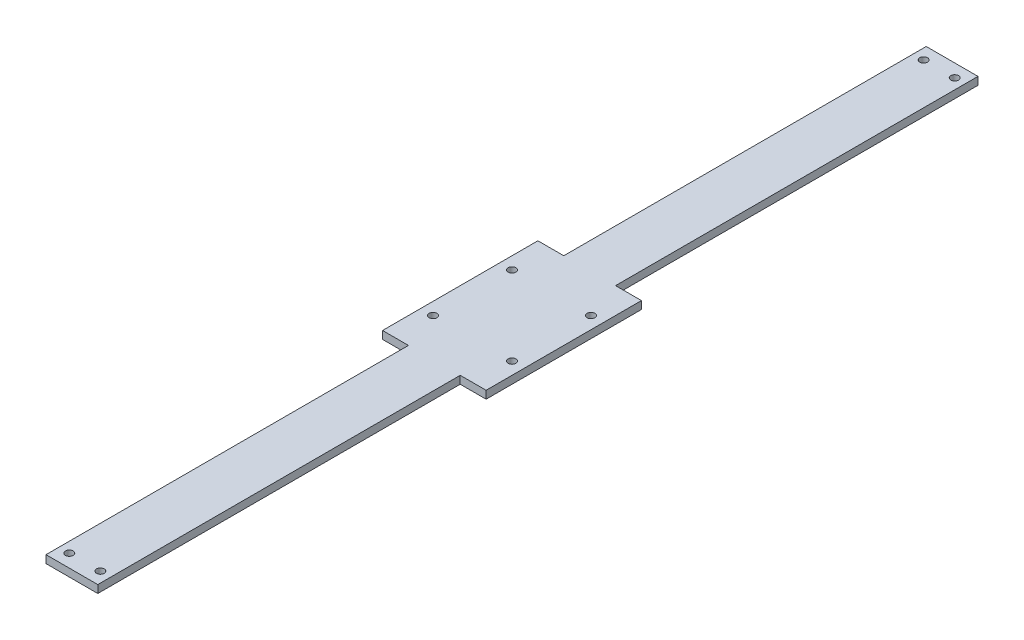
SolidWorks part; units mm, degrees
ref_plane "Front Plane" through (0, 0, 0) normal (0, 0, 1) x (1, 0, 0)
ref_plane "Top Plane" through (0, 0, 0) normal (0, 1, 0) x (1, 0, 0)
ref_plane "Right Plane" through (0, 0, 0) normal (1, 0, 0) x (0, 0, -1)
sketch "Sketch1" plane through (0, 0, 0) normal (0, 1, 0) x (1, 0, 0)
  line L5 (-10, 170) -> (-10, 30)
  line L6 (20, 170) -> (-20, 170) construction
  line L12 (20, 170) -> (20, -170) construction
  line L13 (20, -170) -> (-20, -170) construction
  line L24 (-20, 170) -> (-20, -170) construction
  line L25 (20, 170) -> (-20, -170) construction
  line L26 (20, -170) -> (-20, 170) construction
  line L27 (-10, 30) -> (-20, 30)
  line L28 (0, 170) -> (0, -170) construction
  line L29 (-20, 0) -> (20, 0) construction
  line L30 (10, 30) -> (20, 30)
  line L31 (10, 170) -> (10, 30)
  line L32 (-10, -30) -> (-20, -30)
  line L33 (-10, -170) -> (-10, -30)
  line L34 (10, -170) -> (10, -30)
  line L35 (10, -30) -> (20, -30)
  line L36 (-10, 170) -> (10, 170)
  line L37 (-10, -170) -> (10, -170)
  line L38 (-20, 30) -> (-20, -30)
  line L39 (20, 30) -> (20, -30)
  point P0 (0, 0)
  dimension "D2" = 40
  dimension "D1" = 340
  dimension "D3" = 10
  dimension "D4" = 30
ref_axis "yaw" through (0, 177.4955, 0) along (0, -1, 0)
extrude "Boss-Extrude1" add sketch "Sketch1" along normal mid plane 3
sketch "Sketch4" plane through (0, 1.5, 0) normal (0, 1, 0) x (1, 0, 0)
  line L1 (15.25, 15.25) -> (-15.25, 15.25)
  line L2 (15.25, 15.25) -> (15.25, -15.25)
  line L3 (15.25, -15.25) -> (-15.25, -15.25)
  line L4 (-15.25, 15.25) -> (-15.25, -15.25)
  line L5 (15.25, 15.25) -> (-15.25, -15.25) construction
  line L6 (15.25, -15.25) -> (-15.25, 15.25) construction
  point P0 (0, 0)
  dimension "D1" = 30.5
  dimension "D2" = 30.5
hole_wizard "fc mount hole" positions "Sketch5" profile "Sketch6" hole size "Ø3.0" standard "ISO" end condition through all
sketch "Sketch5" plane through (0, 1.5, 0) normal (0, 1, 0) x (1, 0, 0)
  point P0 (-15.25, 15.25)
  point P3 (15.25, 15.25)
  point P6 (15.25, -15.25)
  point P9 (-15.25, -15.25)
sketch "Sketch6" plane through (-15.25, 1.5, -15.25) normal (1, 0, 0) x (0, 0, 1)
  line L0 (0, 0) -> (0, 3)
  line L1 (0, 3) -> (1.5, 3)
  line L2 (1.5, 3) -> (1.5, 0)
  line L5 (1.5, 0) -> (0, 0)
  line L11 (0, -6.35) -> (0, 107.95) construction
  dimension "Thru Hole Dia." = 3
  dimension "Thru Hole Depth" = 3
sketch "Sketch7" plane through (0, 1.5, 0) normal (0, 1, 0) x (1, 0, 0)
  line L0 (0, -170) -> (0, 170) construction
  line L1 (-10, -170) -> (10, -170) construction
  line L2 (10, 170) -> (-10, 170) construction
  line L3 (-10, -165) -> (10, -165) construction
  line L4 (-10, -30) -> (-10, -170) construction
  line L5 (10, -170) -> (10, -30) construction
  line L6 (-20, 0) -> (20, 0) construction
  line L7 (-20, 30) -> (-20, -30) construction
  line L8 (20, -30) -> (20, 30) construction
  point P12 (-6, -165)
  point P13 (6, -165)
  dimension "D1" = 5
  dimension "D2" = 12
hole_wizard "Ø3.0 (3) Diameter Hole1" positions "Sketch8" profile "Sketch9" hole size "Ø3.0" standard "ISO" end condition through all
sketch "Sketch8" plane through (0, 1.5, 0) normal (0, 1, 0) x (1, 0, 0)
  point P0 (6, -165)
  point P3 (-6, -165)
sketch "Sketch9" plane through (6, 1.5, 165) normal (1, 0, 0) x (0, 0, 1)
  line L0 (0, 0) -> (0, 3)
  line L1 (0, 3) -> (1.5, 3)
  line L2 (1.5, 3) -> (1.5, 0)
  line L5 (1.5, 0) -> (0, 0)
  line L11 (0, -6.35) -> (0, 107.95) construction
  dimension "Thru Hole Dia." = 3
  dimension "Thru Hole Depth" = 3
mirror "Mirror1" about plane through (0, 0, 0) normal (0, 0, 1) of "Ø3.0 (3) Diameter Hole1"
